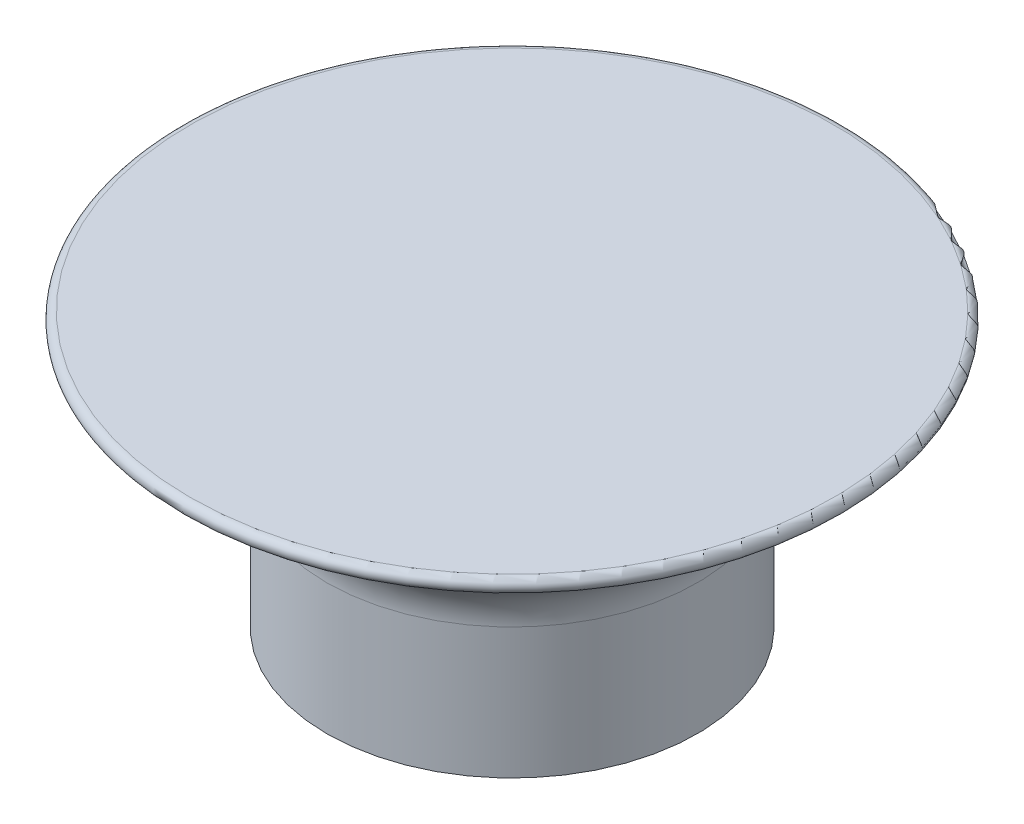
SolidWorks part; units mm, degrees
material "Plain Carbon Steel"
ref_plane "Front Plane" through (0, 0, 0) normal (0, 0, 1) x (1, 0, 0)
ref_plane "Top Plane" through (0, 0, 0) normal (0, 1, 0) x (1, 0, 0)
ref_plane "Right Plane" through (0, 0, 0) normal (1, 0, 0) x (0, 0, -1)
sketch "Sketch1" plane through (0, 0, 0) normal (0, 1, 0) x (1, 0, 0)
  circle A0 centre (0, 0) radius 3.937
  circle A1 centre (0, 0) radius 7.747
  dimension "D1" = 7.874
  dimension "D2" = 3.81
extrude "Boss-Extrude1" add sketch "Sketch1" along normal blind 6.35
ref_plane "Plane1" through (0, 11.43, 0) normal (0, 1, 0) x (1, 0, 0)
sketch "Sketch2" plane through (0, 11.43, 0) normal (0, 1, 0) x (1, 0, 0)
  circle A0 centre (0, 0) radius 14.605
  dimension "D1" = 29.21
sketch "Sketch3" plane through (0, 6.35, 0) normal (0, 1, 0) x (1, 0, 0)
  circle A0 centre (0, 0) radius 7.747 construction
  circle A1 centre (0, 0) radius 7.747
loft "Loft1" add profiles "Sketch3", "Sketch2" connector at (-6.2036, 6.35, 4.6402) connector at (-2.8628, 11.43, 14.3217)
fillet "Fillet1" radius 0.3048 1 edges at (0, 11.43, 14.605)
fillet "Fillet2" radius 2.54 1 edges at (0, 6.35, 7.747)
